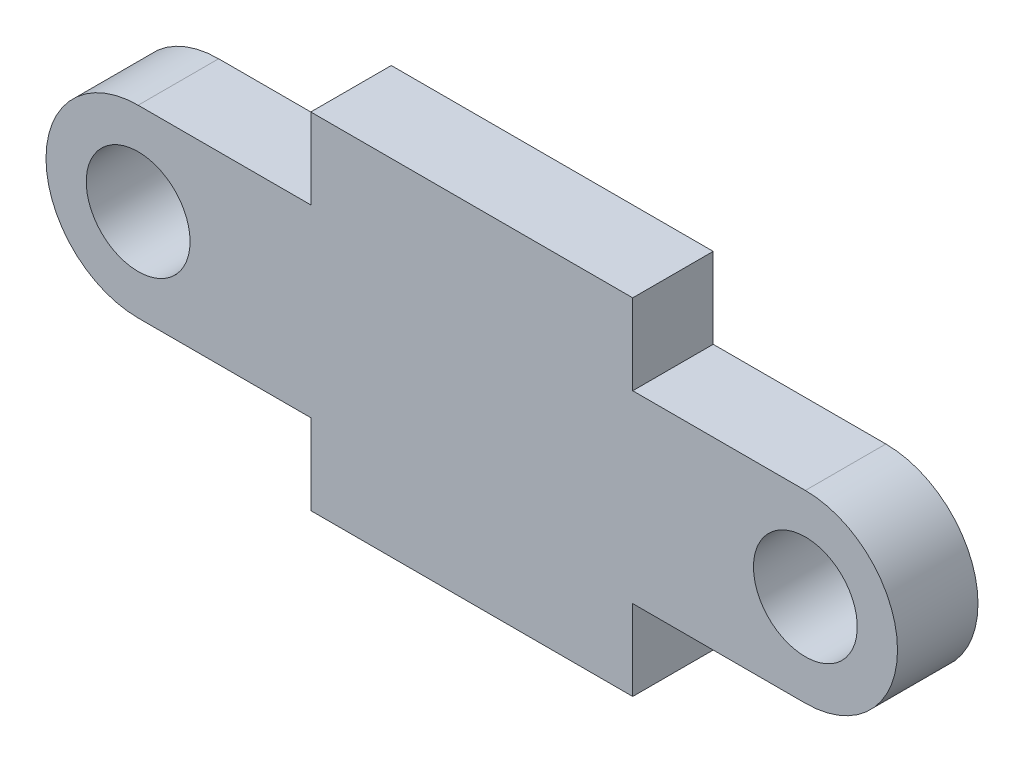
SolidWorks part; units mm, degrees
ref_plane "Front Plane" through (0, 0, 0) normal (0, 0, 1) x (1, 0, 0)
ref_plane "Top Plane" through (0, 0, 0) normal (0, 1, 0) x (1, 0, 0)
ref_plane "Right Plane" through (0, 0, 0) normal (1, 0, 0) x (0, 0, -1)
sketch "Sketch1" plane through (0, 0, 0) normal (0, 0, 1) x (1, 0, 0)
  line L0 (-0.1175, 73.0301) -> (-0.1175, -79.9828) construction
  line L1 (-41.5675, 11.45) -> (-20.1175, 11.45)
  line L2 (-20.1175, 11.45) -> (-20.1175, 21.45)
  line L3 (-20.1175, 21.45) -> (19.8825, 21.45)
  line L4 (-41.5675, -11.45) -> (-20.1175, -11.45)
  line L5 (-20.1175, -11.45) -> (-20.1175, -21.45)
  line L6 (-20.1175, -21.45) -> (19.8825, -21.45)
  line L7 (19.8825, -11.45) -> (19.8825, -21.45)
  line L8 (41.3325, -11.45) -> (19.8825, -11.45)
  line L9 (19.8825, 11.45) -> (19.8825, 21.45)
  line L10 (41.3325, 11.45) -> (19.8825, 11.45)
  circle A0 centre (-41.5675, 0) radius 6.45
  arc A1 (-41.5675, 11.45) -> (-41.5675, -11.45) centre (-41.5675, 0) ccw
  arc A2 (41.3325, 11.45) -> (41.3325, -11.45) centre (41.3325, 0) cw
  circle A3 centre (41.3325, 0) radius 6.45
  point P4 (0, 0)
  point P11 (0, 0)
  point P14 (0, 0)
  point P15 (0, 0)
  point P16 (0, 0)
  point P17 (-30.8425, 11.45)
  point P18 (0, 0)
  point P19 (0, 0)
  point P26 (-0.1175, -21.45)
  point P28 (-0.1175, 21.45)
  dimension "D1" = 12.9
  dimension "D3" = 22.9
  dimension "D7" = 22.9
  dimension "D2" = 41.45
  dimension "D4" = 10
  dimension "D5" = 10
  dimension "D6" = 20
extrude "Boss-Extrude1" add sketch "Sketch1" against normal blind 10
